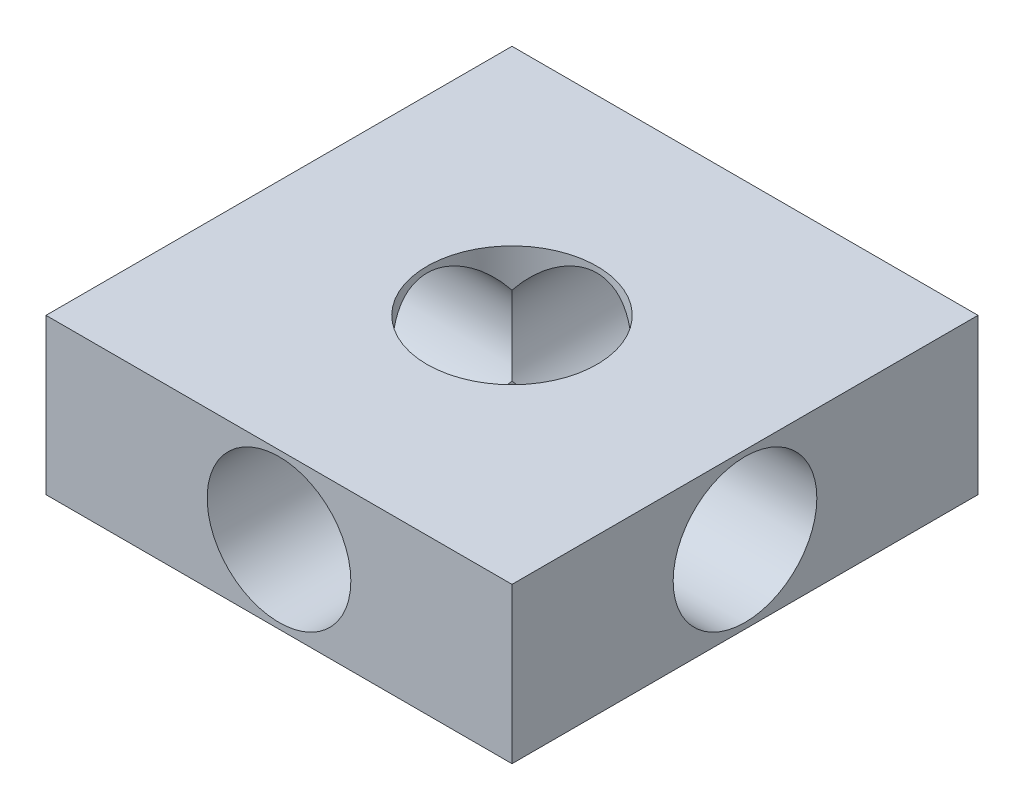
SolidWorks part; units mm, degrees
ref_plane "Front Plane" through (0, 0, 0) normal (0, 0, 1) x (1, 0, 0)
ref_plane "Top Plane" through (0, 0, 0) normal (0, 1, 0) x (1, 0, 0)
ref_plane "Right Plane" through (0, 0, 0) normal (1, 0, 0) x (0, 0, -1)
sketch "Sketch1" plane through (0, 0, 0) normal (0, 1, 0) x (1, 0, 0)
  circle A0 centre (0, 0) radius 11
  dimension "D1" = 22
extrude "Boss-Extrude1" add sketch "Sketch1" along normal blind 10
sketch "Sketch13" plane through (0, 10, 0) normal (0, 1, 0) x (1, 0, 0)
  line L1 (30, -30) -> (-30, -30)
  line L2 (30, -30) -> (30, 30)
  line L3 (30, 30) -> (-30, 30)
  line L4 (-30, -30) -> (-30, 30)
  line L5 (30, -30) -> (-30, 30) construction
  line L6 (30, 30) -> (-30, -30) construction
  point P0 (0, 0)
  dimension "D1" = 60
  dimension "D2" = 60
extrude "Boss-Extrude5" add sketch "Sketch13" along normal blind 20
sketch "Face 1" plane through (0, 0, 30) normal (0, 0, 1) x (1, 0, 0)
  line L0 (0, 10) -> (0, 30) construction
  line L1 (-30, 10) -> (30, 10) construction
  line L2 (-30, 30) -> (30, 30) construction
  circle A0 centre (0, 20) radius 9.25
sketch "Face 2" plane through (30, 0, 0) normal (1, 0, 0) x (0, 0, -1)
  line L0 (0, 10) -> (0, 30) construction
  line L1 (-30, 10) -> (30, 10) construction
  line L2 (-30, 30) -> (30, 30) construction
  circle A0 centre (0, 20) radius 9.25
  dimension "D1" = 18.5
sketch "Face 3" plane through (-30, 0, 0) normal (-1, 0, 0) x (0, 0, 1)
  line L0 (0, 10) -> (0, 30) construction
  line L1 (-30, 10) -> (30, 10) construction
  line L2 (-30, 30) -> (30, 30) construction
  circle A0 centre (0, 20) radius 9.25
  dimension "D1" = 18.5
extrude "Cut-Extrude1" cut sketch "Face 1" against normal blind 20
extrude "Cut-Extrude2" cut sketch "Face 3" against normal blind 20
extrude "Cut-Extrude3" cut sketch "Face 2" against normal blind 20
sketch "Sketch14" plane through (0, 0, 0) normal (0, -1, 0) x (1, 0, 0)
  line L0 (11, 0) -> (-11, 0) construction
  line L1 (0, -11) -> (0, 11) construction
  circle A0 centre (0, 0) radius 11 construction
  circle A1 centre (-7.94, 0) radius 1.42
  circle A2 centre (0, 7.94) radius 1.42
  circle A3 centre (7.94, 0) radius 1.42
  circle A4 centre (0, -7.94) radius 1.42
  point P7 (0, 7.94)
  point P8 (7.94, 0)
  point P9 (0, -7.94)
  point P10 (-7.94, 0)
  dimension "D5" = 2.84
  dimension "D1" = 3.06
  dimension "D2" = 3.06
  dimension "D3" = 3.06
  dimension "D4" = 3.06
extrude "Cut-Extrude4" cut sketch "Sketch14" against normal blind 21
sketch "Sketch15" plane through (0, 30, 0) normal (0, 1, 0) x (1, 0, 0)
  line L0 (30, 0) -> (-30, 0) construction
  line L1 (30, -30) -> (30, 30) construction
  line L2 (-30, 30) -> (-30, -30) construction
  line L3 (0, -30) -> (0, 30) construction
  line L4 (-30, -30) -> (30, -30) construction
  line L5 (30, 30) -> (-30, 30) construction
  line L6 (-7.94, 0) -> (-30, 0) construction
  circle A0 centre (-7.94, 0) radius 1.42
  circle A1 centre (0, 7.94) radius 1.42
  circle A2 centre (7.94, 0) radius 1.42
  circle A3 centre (0, -7.94) radius 1.42
  dimension "D5" = 2.84
  dimension "D1" = 22.06
  dimension "D2" = 22.06
  dimension "D3" = 22.06
  dimension "D4" = 22.06
extrude "Cut-Extrude5" cut sketch "Sketch15" against normal blind 22
sketch "Sketch17" plane through (0, 30, 0) normal (0, 1, 0) x (1, 0, 0)
  circle A0 centre (0, 0) radius 10.95
  dimension "D1" = 21.9
extrude "Cut-Extrude10" cut sketch "Sketch17" against normal blind 18
sketch "Sketch18" plane through (10, 0, 0) normal (1, 0, 0) x (0, 0, -1)
  circle A0 centre (0, 20) radius 9.25
extrude "Cut-Extrude11" cut sketch "Sketch18" against normal mid plane 113
sketch "Sketch19" plane through (0, 0, 30) normal (0, 0, 1) x (1, 0, 0)
  circle A0 centre (0, 20) radius 9.25
extrude "Cut-Extrude12" cut sketch "Sketch19" against normal blind 113
